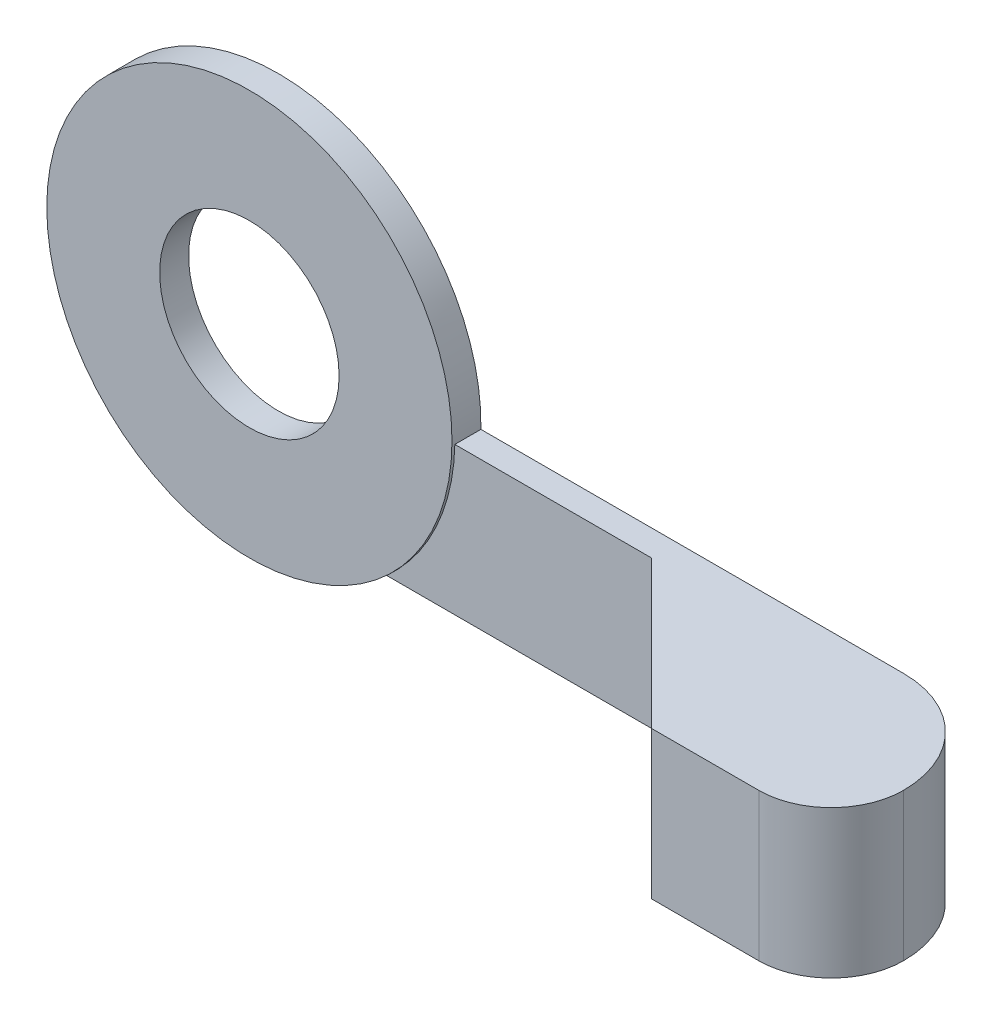
SolidWorks part; units mm, degrees
ref_plane "Front" through (0, 0, 0) normal (0, 0, 1) x (1, 0, 0)
ref_plane "Top" through (0, 0, 0) normal (0, 1, 0) x (1, 0, 0)
ref_plane "Right" through (0, 0, 0) normal (1, 0, 0) x (0, 0, -1)
sketch "Sketch3" plane through (0, 0, 0) normal (0, 1, 0) x (1, 0, 0)
  line L0 (0, -2.5) -> (-3.7, -2.5)
  line L1 (-3.7, -2.5) -> (-3.7, 3.5)
  line L2 (-3.7, 3.5) -> (-1, 3.5)
  arc A0 (2.5, 0) -> (0, -2.5) centre (0, 0) cw
  arc A1 (-1, 3.5) -> (2.5, 0) centre (-1, 0) cw
  point P9 (-0.9646, 0.0881)
  point P10 (-1.1517, -0.1632)
  point P11 (0, 0)
  dimension "D1" = 2.5
  dimension "D2" = 6.2
  dimension "D3" = 6
extrude "Boss-Extrude1" add sketch "Sketch3" along normal blind 5.1
sketch "Sketch4" plane through (-3.7, 0, 0) normal (-1, 0, 0) x (0, 0, 1)
  line L1 (-3.5, 5.1) -> (-2.6, 5.1)
  line L2 (-3.5, 5.1) -> (-3.5, 0)
  line L3 (-3.5, 0) -> (-2.6, 0)
  line L4 (-2.6, 5.1) -> (-2.6, 0)
  dimension "D1" = 0.9
extrude "Boss-Extrude2" add sketch "Sketch4" along normal blind 18.9
sketch "Sketch5" plane through (0, 0, -3.5) normal (0, 0, -1) x (-1, 0, 0)
  line L0 (22.6, 5.1) -> (22.6, 0) construction
  line L2 (1, 5.1) -> (22.6, 5.1) construction
  circle A0 centre (22.6, 5.25) radius 7
  point P2 (0, 0)
  point P5 (22.6, 5.6625)
  dimension "D2" = 14
  dimension "D1" = 0.15
extrude "Boss-Extrude3" add sketch "Sketch5" against normal blind 1
sketch "Sketch6" plane through (0, 0, -2.6) normal (0, 0, 1) x (1, 0, 0)
  circle A0 centre (-22.6, 5.25) radius 3.1
  circle A1 centre (-22.6, 5.25) radius 7 construction
  dimension "D1" = 6.2
extrude "Cut-Extrude1" cut sketch "Sketch6" against normal through all both and the other way through all
sketch "Sketch7" plane through (0, 0, 0) normal (0, -1, 0) x (1, 0, 0)
  line L0 (-3.7, 2.5) -> (-8.8, -2.6)
  line L1 (-17.9699, -2.6) -> (-3.7, -2.6) construction
  line L2 (-8.8, -2.6) -> (-3.7, -2.6)
  line L3 (-3.7, -2.6) -> (-3.7, 2.5)
  dimension "D1" = 5.1
extrude "Boss-Extrude4" add sketch "Sketch7" against normal up to surface (5.1 mm away) up to face at (-5.1229, 5.1, -1.0582)
